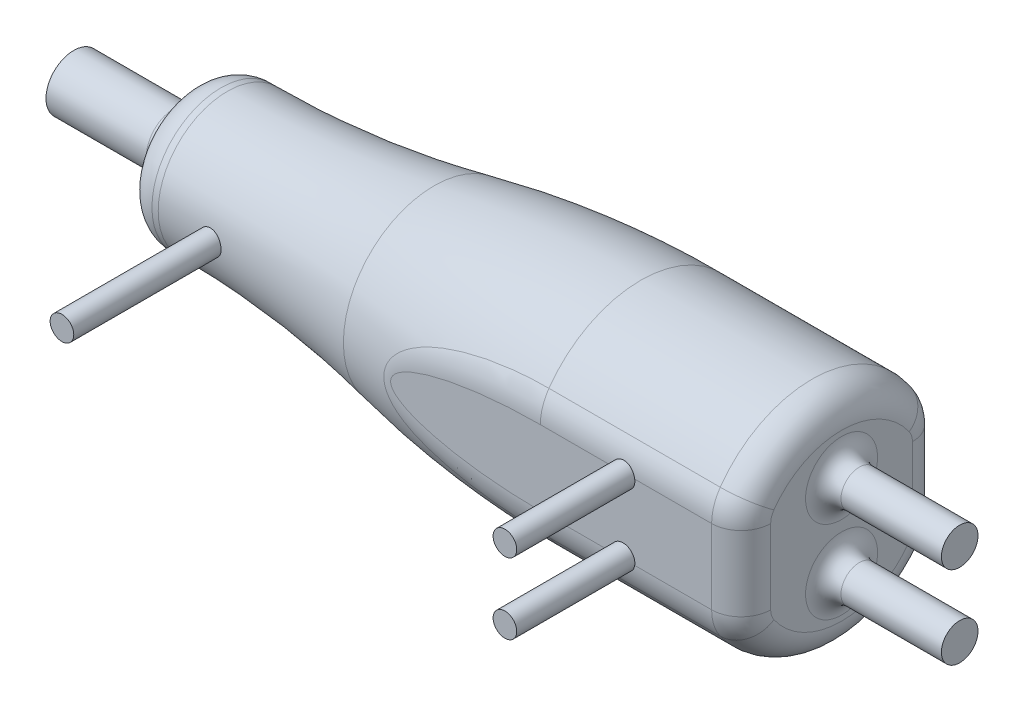
SolidWorks part; units mm, degrees
ref_plane "Plan de face" through (0, 0, 0) normal (0, 0, 1) x (1, 0, 0)
ref_plane "Plan de dessus" through (0, 0, 0) normal (0, 1, 0) x (1, 0, 0)
ref_plane "Plan de droite" through (0, 0, 0) normal (1, 0, 0) x (0, 0, -1)
sketch "Esquisse1" plane through (0, 0, 0) normal (0, 0, 1) x (1, 0, 0)
  line L0 (0, 0) -> (43.1861, 0) construction
  line L1 (100, 7) -> (18.5305, 7) construction
  line L2 (100, 7) -> (130, 7)
  spline S0 degree 3 poles (0, 0) (6.6829, 0) (35.3567, 0.7944) (64.6227, 6.2056) (93.5456, 7) (100, 7) knots 0 0 0 0 0.4161 0.5839 1 1 1 1
  dimension "D1" = 7
  dimension "D2" = 100
  dimension "D3" = 41.6667
  dimension "D4" = 41.6667
  dimension "D5" = 2.3333
  dimension "D6" = 2.3333
  dimension "D7" = 30
sketch "Esquisse2" plane through (0, 0, 0) normal (1, 0, 0) x (0, 0, -1)
  circle A0 centre (0, 0) radius 3.1
  dimension "D1" = 6.2
sweep "Balayage3" add profiles "Esquisse2" path "Esquisse1"
mirror "Symétrie1" about plane through (0, 0, 0) normal (0, 1, 0) of "Balayage3"
sketch "Esquisse7" plane through (0, 0, 0) normal (0, 0, 1) x (1, 0, 0)
  line L0 (0, 0) -> (0, 4.7) construction
  line L2 (0, 0) -> (43.1861, 0) construction
  line L3 (0, 0) -> (110, 0)
  line L4 (0, 4.7) -> (27.4824, 4.7) construction
  line L5 (76, 19) -> (40.1517, 19) construction
  line L6 (6, 11.7) -> (0, 11.7)
  line L8 (76, 19) -> (110, 19)
  line L9 (110, 19) -> (110, 0)
  line L10 (0, 4.7) -> (-20, 4.7)
  line L11 (-20, 4.7) -> (-20, 0)
  line L12 (-20, 0) -> (0, 0)
  line L14 (0, 11.7) -> (0, 4.7)
  line L15 (130, 3.9) -> (130, 10.1) construction
  line L16 (100, 7) -> (130, 7) construction
  arc A1 (6, 11.7) -> (41, 15.35) centre (6, 181.3332) ccw
  arc A2 (41, 15.35) -> (76, 19) centre (76, -150.6332) cw
  dimension "D1" = 4.7
  dimension "D2" = 20
  dimension "D4" = 7
  dimension "D6" = 6
  dimension "D3" = 12
  dimension "D5" = 70
  dimension "D7" = 20
revolve "Révolution1" add sketch "Esquisse7" angle 360 about L3
sketch "Esquisse8" plane through (110, 0, 0) normal (1, 0, 0) x (0, 0, -1)
  line L0 (0, 15) -> (0, -15) construction
  line L1 (-17, 8.4853) -> (-17, -8.4853)
  line L2 (17, 8.4853) -> (17, -8.4853)
  circle A0 centre (0, 0) radius 19 construction
  arc A1 (-17, -8.4853) -> (17, -8.4853) centre (0, 0) ccw construction
  arc A2 (-17, 8.4853) -> (17, 8.4853) centre (0, 0) cw construction
  arc A3 (-17, -8.4853) -> (-17, 8.4853) centre (0, 0) cw
  arc A4 (17, 8.4853) -> (17, -8.4853) centre (0, 0) cw
  dimension "D1" = 17
extrude "Enlèv. mat.-Extru.1" cut sketch "Esquisse8" against normal through all
fillet "Congé4" radius 8 6 edges at (93, 8.4853, -17) (93, -8.4853, -17) (101.9551, 0.296, -17) (93, -8.4853, 17) (93, 8.4853, 17) (101.9551, -0.296, 17)
fillet "Congé5" radius 3 3 edges at (110, -7, 3.1) (110, 7, 3.1) (0, 0, 4.7)
fillet "Congé6" radius 5 9 edges at (110, -8.7366, -16.6277) (110, 0, -17) (110, 8.7366, -16.6277) (110, 19, 0) (110, 8.7366, 16.6277) (110, 0, 17) (110, -8.7366, 16.6277) (110, -19, 0) (0, 0, 11.7)
sketch "Esquisse9" plane through (0, 0, 17) normal (0, 0, 1) x (1, 0, 0)
  line L0 (0, 0) -> (43.1861, 0) construction
  line L1 (0, 0) -> (110, 0) construction
  line L2 (110, 6.3246) -> (110, -6.3246) construction
  line L3 (0, -3.1) -> (0, 3.1) construction
  circle A0 centre (90, 6) radius 2
  circle A1 centre (15, 0) radius 2
  circle A2 centre (90, -6) radius 2
  spline S1 degree 3 poles (0, 0) (6.6829, 0) (35.3567, 0.7944) (64.6227, 6.2056) (93.5456, 7) (100, 7) knots 0 0 0 0 0.4161 0.5839 1 1 1 1 construction
  dimension "D1" = 4
  dimension "D2" = 75
  dimension "D3" = 12
  dimension "D4" = 15
extrude "Boss.-Extru.1" add sketch "Esquisse9" along normal blind 20 and the other way up to next
equation "\"D3@Esquisse1\"=\"D2@Esquisse1\"/2.4"
equation "\"D4@Esquisse1\"=\"D2@Esquisse1\"/2.4"
equation "\"D5@Esquisse1\"=\"D1@Esquisse1\"/3"
equation "\"D6@Esquisse1\"=\"D1@Esquisse1\"/3"
